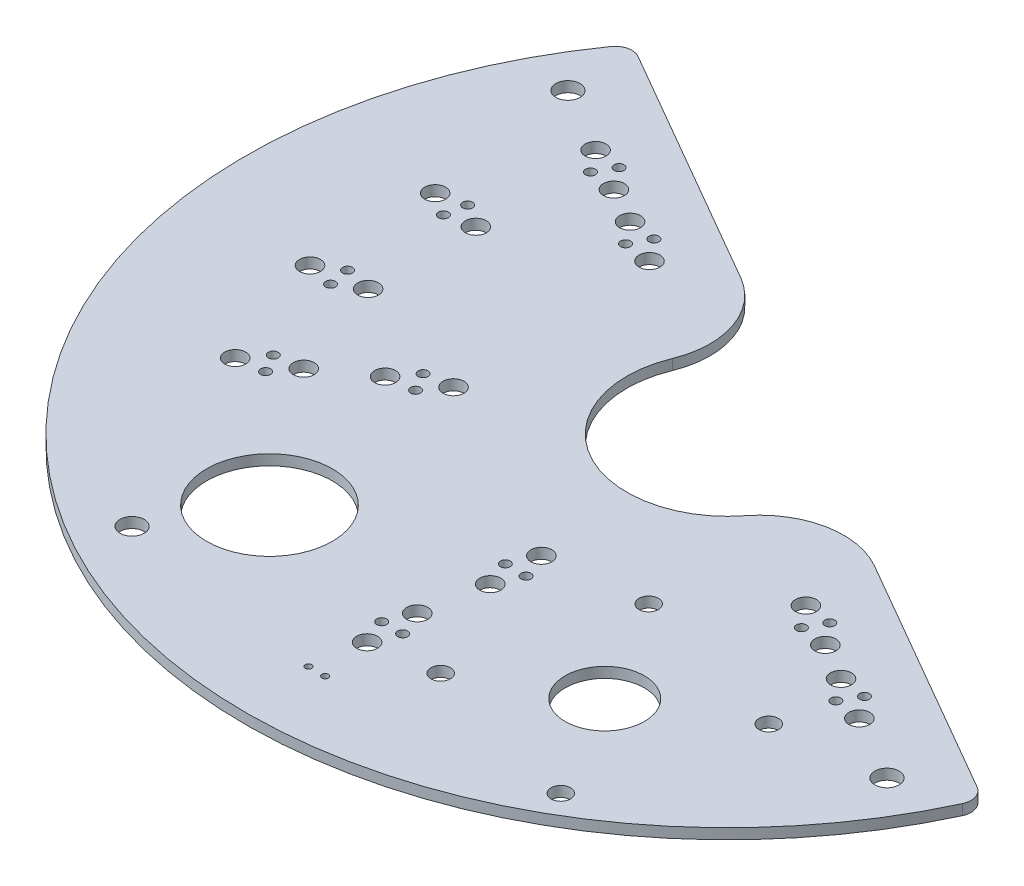
SolidWorks part; units mm, degrees
ref_plane "Front Plane" through (0, 0, 0) normal (0, 0, 1) x (1, 0, 0)
ref_plane "Top Plane" through (0, 0, 0) normal (0, 1, 0) x (1, 0, 0)
ref_plane "Right Plane" through (0, 0, 0) normal (1, 0, 0) x (0, 0, -1)
sketch "Sketch1" plane through (0, 0, 0) normal (0, 1, 0) x (1, 0, 0)
  line L0 (0, 50.8) -> (0, 59.6199) construction
  line L1 (0, 50.8) -> (11.3081, 50.8) construction
  line L2 (0, 0) -> (0, 47) construction
  line L3 (0, 0) -> (-46.286, 8.1615) construction
  line L4 (0, 0) -> (0, 47) construction
  line L5 (0, 0) -> (-46.286, -8.1615) construction
  line L6 (-30.1951, -16.4814) -> (-38.7564, -18.616) construction
  line L7 (1.7716, -33.8648) -> (4.3514, -25.4269) construction
  line L8 (31.2901, -20.38) -> (25.051, -14.141) construction
  line L9 (-31.8057, 17.1605) -> (-38.0448, 23.3996) construction
  circle A0 centre (0, 0) radius 50.8 construction
  circle A1 centre (0, 0) radius 15.24
  circle A2 centre (0, 0) radius 73.025
  circle A3 centre (0, 50.8) radius 6.3 construction
  circle A4 centre (25.4, 43.9941) radius 6.3 construction
  circle A5 centre (43.9941, 25.4) radius 6.3 construction
  circle A6 centre (50.8, 0) radius 6.3 construction
  circle A7 centre (43.9941, -25.4) radius 6.3 construction
  circle A8 centre (25.4, -43.9941) radius 6.3 construction
  circle A9 centre (0, -50.8) radius 6.3 construction
  circle A10 centre (-25.4, -43.9941) radius 6.3 construction
  circle A11 centre (-43.9941, -25.4) radius 6.3 construction
  circle A12 centre (-50.8, 0) radius 6.3 construction
  circle A13 centre (-43.9941, 25.4) radius 6.3 construction
  circle A14 centre (-25.4, 43.9941) radius 6.3 construction
  circle A15 centre (0, 50.8) radius 1.585 construction
  circle A16 centre (-1.585, 50.8) radius 0.75
  circle A17 centre (1.585, 50.8) radius 0.75
  circle A18 centre (0, 50.8) radius 3.8 construction
  circle A19 centre (0, 54.6) radius 1.585
  circle A20 centre (0, 47) radius 1.585
  circle A21 centre (47.285, 27.3) radius 1.585
  circle A22 centre (43.2016, 26.7727) radius 0.75
  circle A23 centre (44.7866, 24.0273) radius 0.75
  circle A24 centre (40.7032, 23.5) radius 1.585
  circle A25 centre (47.285, -27.3) radius 1.585
  circle A26 centre (44.7866, -24.0273) radius 0.75
  circle A27 centre (43.2016, -26.7727) radius 0.75
  circle A28 centre (40.7032, -23.5) radius 1.585
  circle A29 centre (0, -54.6) radius 1.585
  circle A30 centre (1.585, -50.8) radius 0.75
  circle A31 centre (-1.585, -50.8) radius 0.75
  circle A32 centre (0, -47) radius 1.585
  circle A33 centre (-47.285, -27.3) radius 1.585
  circle A34 centre (-43.2016, -26.7727) radius 0.75
  circle A35 centre (-44.7866, -24.0273) radius 0.75
  circle A36 centre (-40.7032, -23.5) radius 1.585
  circle A37 centre (-47.285, 27.3) radius 1.585
  circle A38 centre (-44.7866, 24.0273) radius 0.75
  circle A39 centre (-43.2016, 26.7727) radius 0.75
  circle A40 centre (-40.7032, 23.5) radius 1.585
  circle A41 centre (25.4, 43.9941) radius 20
  circle A42 centre (-25.4, -43.9941) radius 9.525
  circle A43 centre (25.4, -43.9941) radius 6
  circle A44 centre (-46.286, 8.1615) radius 1.585
  circle A45 centre (-50.3035, 7.2604) radius 0.75
  circle A46 centre (-49.753, 10.3822) radius 0.75
  circle A47 centre (-53.7705, 9.4812) radius 1.585
  circle A48 centre (-46.286, -8.1615) radius 1.585
  circle A49 centre (-49.753, -10.3822) radius 0.75
  circle A50 centre (-50.3035, -7.2604) radius 0.75
  circle A51 centre (-53.7705, -9.4812) radius 1.585
  circle A52 centre (-30.191, -16.4817) radius 6.3 construction
  circle A53 centre (-30.191, -16.4817) radius 1.585 construction
  circle A54 centre (-29.3973, -17.8553) radius 0.75
  circle A55 centre (-31.002, -15.1168) radius 0.75
  circle A56 centre (-30.191, -16.4817) radius 3.8 construction
  circle A57 centre (-33.5032, -18.378) radius 1.585
  circle A58 centre (-26.9143, -14.5903) radius 1.585
  circle A59 centre (1.7693, -33.8681) radius 6.3 construction
  circle A60 centre (1.7693, -33.8681) radius 1.585 construction
  circle A61 centre (0.1831, -33.841) radius 0.75
  circle A62 centre (3.3569, -33.8759) radius 0.75
  circle A63 centre (1.7693, -33.8681) radius 3.8 construction
  circle A64 centre (1.8498, -30.0524) radius 1.585
  circle A65 centre (1.7028, -37.651) radius 1.585
  circle A66 centre (31.7545, -18.4007) radius 6.3 construction
  circle A67 centre (31.7545, -18.4007) radius 1.585 construction
  circle A68 centre (30.9859, -19.7885) radius 0.75
  circle A69 centre (32.5067, -17.0026) radius 0.75
  circle A70 centre (31.7545, -18.4007) radius 3.8 construction
  circle A71 centre (28.4231, -16.5382) radius 1.585
  circle A72 centre (35.0633, -20.2353) radius 1.585
  circle A73 centre (-31.9359, 18.6471) radius 6.3 construction
  circle A74 centre (-31.9359, 18.6471) radius 1.585 construction
  circle A75 centre (-32.7045, 17.2593) radius 0.75
  circle A76 centre (-31.1837, 20.0452) radius 0.75
  circle A77 centre (-31.9359, 18.6471) radius 3.8 construction
  circle A78 centre (-35.2672, 20.5095) radius 1.585
  circle A79 centre (-28.627, 16.8125) radius 1.585
  point P50 (0, 0)
  point P84 (0, 0)
  dimension "D1" = 12
  dimension "D2" = 101.6
  dimension "D3" = 3.17
  dimension "D4" = 1.5
  dimension "D5" = 7.6
  dimension "D6" = 6
  dimension "D7" = 3.17
  dimension "D8" = 40
  dimension "D9" = 19.05
  dimension "D10" = 12
  dimension "D11" = 146.05
  dimension "D12" = 30.48
  dimension "D14" = 80
  dimension "D16" = 100
  dimension "D13" = 2
  dimension "D15" = 2
extrude "Boss-Extrude1" add sketch "Sketch1" against normal blind 1.5875
sketch "Sketch2" plane through (0, 0, 0) normal (0, 1, 0) x (1, 0, 0)
  line L0 (0, 0) -> (0, 66.04) construction
  line L1 (0, 0) -> (-57.1923, 33.02) construction
  circle A0 centre (0, 0) radius 66.04 construction
  circle A1 centre (0, 66.04) radius 1.8288 construction
  circle A2 centre (-57.1923, 33.02) radius 1.8288
  circle A3 centre (33.02, 57.1923) radius 1.8288
  circle A4 centre (57.1923, -33.02) radius 1.8288
  circle A5 centre (-33.02, -57.1923) radius 1.8288
  point P17 (0, 0)
  dimension "D1" = 132.08
  dimension "D2" = 3.6576
  dimension "D3" = 2
  dimension "D4" = 60
  dimension "D5" = 4
extrude "Cut-Extrude1" cut sketch "Sketch2" against normal through all
sketch "Sketch3" plane through (0, 0, 0) normal (0, 1, 0) x (1, 0, 0)
  line L0 (-57.1923, 33.02) -> (57.1923, -33.02) construction
  line L1 (-59.5338, 44.6372) -> (68.4238, -29.2392)
  line L2 (-52.7473, 40.719) -> (61.6373, -25.321) construction
  arc A0 (68.4238, -29.2392) -> (-59.5338, 44.6372) centre (0, 0) ccw
  dimension "D1" = 8.89
extrude "Cut-Extrude2" cut sketch "Sketch3" against normal through all
fillet "Fillet1" radius 12.7 2 edges at (15.165, -0.7937, -1.5098) (-6.275, -0.7937, -13.8882)
fillet "Fillet2" radius 2.54 2 edges at (67.2161, -0.7937, 28.542) (-58.3261, -0.7937, -43.9399)
sketch "Sketch4" plane through (0, 0, 0) normal (0, 1, 0) x (1, 0, 0)
  line L0 (0, 0) -> (0, -73.025) construction
  arc A0 (-59.6949, 42.0615) -> (66.2738, -30.6666) centre (0, 0) ccw construction
  circle A1 centre (0, 0) radius 62.23 construction
  circle A2 centre (0, -62.23) radius 0.4953 construction
  circle A3 centre (1.27, -62.23) radius 0.4953
  circle A4 centre (-1.27, -62.23) radius 0.4953
  dimension "D1" = 0.9906
  dimension "D4" = 124.46
  dimension "D2" = 2
  dimension "D3" = 2
extrude "Cut-Extrude3" cut sketch "Sketch4" against normal through all
sketch "Sketch5" plane through (0, -1.5875, 0) normal (0, -1, 0) x (1, 0, 0)
  line L0 (34.4907, 15.2341) -> (45.0238, 21.3018)
  line L1 (-31.0536, -21.3854) -> (-30.5378, -22.2779)
  line L2 (-30.0652, -20.8147) -> (-29.5513, -21.704)
  line L3 (-30.5378, -22.2779) -> (-40.9598, -28.3409)
  line L13 (33.3365, 26.1699) -> (41.5359, 31.0198)
  line L14 (28.0125, 9.134) -> (57.7422, 26.2984)
  line L29 (46.7892, 22.3211) -> (54.7743, 26.9312)
  line L30 (29.0711, 12.1121) -> (33.5009, 14.6639)
  line L31 (6.096, 41.9407) -> (6.096, 51.4811)
  line L32 (32.4795, 23.822) -> (40.9598, 28.3409)
  line L33 (-6.096, 38.6381) -> (-6.096, 51.4811)
  line L34 (4.064, 40.0736) -> (4.064, 49.6426)
  line L35 (-21.9165, -19.6925) -> (-41.5359, -31.0198)
  line L39 (-4.064, 36.8606) -> (-4.064, 49.6426)
  line L40 (-30.4135, 24.5983) -> (-41.5359, 31.0198)
  line L42 (-29.8903, 21.9498) -> (-40.9598, 28.3409)
  line L93 (-25.0455, -19.0828) -> (-29.5513, -21.704)
  arc A0 (1.2946, 63.4357) -> (1.2454, 61.0243) centre (1.27, 62.23) ccw
  arc A1 (-1.1373, 61.0264) -> (-1.1844, 63.4379) centre (-1.27, 62.23) ccw
  arc A2 (-1.1373, 61.0264) -> (-54.0489, -28.3589) centre (0, 0) ccw
  arc A3 (-1.1844, 63.4379) -> (-56.1144, -29.6131) centre (0, 0) ccw
  arc A4 (54.7743, 26.9312) -> (1.2454, 61.0243) centre (0, 0) ccw
  arc A5 (-56.1144, -29.6131) -> (-54.0489, -28.3589) centre (-55.1689, -28.8424) ccw
  arc A6 (6.096, 51.4811) -> (2.3857, 51.7858) centre (0, 0) ccw
  arc A7 (32.4795, 23.822) -> (4.064, 40.0736) centre (0, 0) ccw
  arc A8 (2.3857, 51.7858) -> (2.3071, 49.7553) centre (1.585, 50.8) ccw
  arc A9 (-2.3071, 49.7553) -> (-2.3857, 51.7858) centre (-1.585, 50.8) ccw
  arc A10 (-48.5987, -10.912) -> (-50.5848, -11.342) centre (-49.753, -10.3822) ccw
  arc A11 (-51.4133, -6.6431) -> (-49.4, -6.3679) centre (-50.3035, -7.2604) ccw
  arc A12 (46.0407, 23.8268) -> (44.2429, 22.8796) centre (44.7866, 24.0273) ccw
  arc A13 (41.9358, 26.8756) -> (43.655, 27.959) centre (43.2016, 26.7727) ccw
  arc A14 (-49.4, 6.3679) -> (-51.4133, 6.6431) centre (-50.3035, 7.2604) ccw
  arc A15 (-50.5848, 11.342) -> (-48.5987, 10.912) centre (-49.753, 10.3822) ccw
  arc A16 (57.7422, 26.2984) -> (1.2946, 63.4357) centre (0, 0) ccw
  arc A17 (-2.3857, 51.7858) -> (-6.096, 51.4811) centre (0, 0) ccw
  arc A18 (-2.3071, 49.7553) -> (-4.064, 49.6426) centre (0, 0) ccw
  arc A19 (45.0238, 21.3018) -> (44.2429, 22.8796) centre (0, 0) ccw
  arc A20 (29.0711, 12.1121) -> (-25.0455, -19.0828) centre (2.3366, -4.0471) ccw
  arc A21 (28.0125, 9.134) -> (-21.9165, -19.6925) centre (2.3859, -4.1326) ccw
  arc A22 (46.7892, 22.3211) -> (46.0407, 23.8268) centre (0, 0) ccw
  arc A23 (43.655, 27.959) -> (41.5359, 31.0198) centre (0, 0) ccw
  arc A24 (-46.0407, -23.8268) -> (-44.2429, -22.8796) centre (-44.7866, -24.0273) ccw
  arc A25 (-41.9358, -26.8756) -> (-43.655, -27.959) centre (-43.2016, -26.7727) ccw
  arc A26 (41.9358, 26.8756) -> (40.9598, 28.3409) centre (0, 0) ccw
  circle A27 centre (1.27, 62.23) radius 0.4953
  arc A28 (-43.655, 27.959) -> (-41.9358, 26.8756) centre (-43.2016, 26.7727) ccw
  arc A29 (-44.2429, 22.8796) -> (-46.0407, 23.8268) centre (-44.7866, 24.0273) ccw
  circle A30 centre (-1.27, 62.23) radius 0.4953
  arc A31 (-43.655, -27.959) -> (-41.5359, -31.0198) centre (0, 0) ccw
  circle A32 centre (-26.7727, 43.2016) radius 1.27 [skipped]
  circle A33 centre (-24.0273, 44.7866) radius 1.27 [skipped]
  circle A34 centre (24.0273, 44.7866) radius 1.27 [skipped]
  circle A35 centre (26.7727, 43.2016) radius 1.27 [skipped]
  circle A36 centre (50.8, 1.585) radius 1.27 [skipped]
  circle A37 centre (50.8, -1.585) radius 1.27 [skipped]
  circle A38 centre (44.7866, -24.0273) radius 1.27 [skipped]
  circle A39 centre (43.2016, -26.7727) radius 1.27 [skipped]
  circle A40 centre (26.7727, -43.2016) radius 1.27 [skipped]
  circle A41 centre (24.0273, -44.7866) radius 1.27 [skipped]
  circle A42 centre (1.585, -50.8) radius 1.27 [skipped]
  circle A43 centre (-1.585, -50.8) radius 1.27 [skipped]
  circle A44 centre (-24.0273, -44.7866) radius 1.27 [skipped]
  circle A45 centre (-26.7727, -43.2016) radius 1.27 [skipped]
  circle A46 centre (-50.8, 1.585) radius 1.27 [skipped]
  circle A47 centre (-50.8, -1.585) radius 1.27 [skipped]
  arc A48 (-41.9358, -26.8756) -> (-40.9598, -28.3409) centre (0, 0) ccw
  arc A49 (-40.9598, 28.3409) -> (-41.9358, 26.8756) centre (0, 0) ccw
  arc A50 (33.3365, 26.1699) -> (6.096, 41.9407) centre (0, 0) ccw
  circle A51 centre (1.585, 50.8) radius 0.75
  arc A52 (-46.0407, 23.8268) -> (-47.6319, 20.4612) centre (0, 0) ccw
  arc A53 (4.064, 49.6426) -> (2.3071, 49.7553) centre (0, 0) ccw
  arc A54 (-41.5359, 31.0198) -> (-43.655, 27.959) centre (0, 0) ccw
  arc A55 (-6.096, 38.6381) -> (-30.4135, 24.5983) centre (0, 0) ccw
  arc A56 (-4.064, 36.8606) -> (-29.8903, 21.9498) centre (0, 0) ccw
  arc A57 (-44.2429, 22.8796) -> (-48.5987, 10.912) centre (0, 0) ccw
  circle A58 centre (-1.585, 50.8) radius 0.75
  circle A59 centre (43.2016, 26.7727) radius 0.75
  arc A60 (-47.6319, 20.4612) -> (-50.5848, 11.342) centre (0, 0) ccw
  arc A61 (-51.4133, 6.6431) -> (-51.4133, -6.6431) centre (0, 0) ccw
  arc A62 (-49.4, 6.3679) -> (-49.4, -6.3679) centre (0, 0) ccw
  circle A63 centre (44.7866, 24.0273) radius 0.75
  arc A64 (-50.5848, -11.342) -> (-46.0407, -23.8268) centre (0, 0) ccw
  arc A65 (-48.5987, -10.912) -> (-44.2429, -22.8796) centre (0, 0) ccw
  circle A66 centre (-43.2016, 26.7727) radius 0.75
  circle A67 centre (-44.7866, 24.0273) radius 0.75
  circle A68 centre (-49.753, 10.3822) radius 0.75
  circle A69 centre (-50.3035, 7.2604) radius 0.75
  circle A70 centre (-50.3035, -7.2604) radius 0.75
  circle A71 centre (-49.753, -10.3822) radius 0.75
  circle A72 centre (-44.7866, -24.0273) radius 0.75
  circle A73 centre (-43.2016, -26.7727) radius 0.75
  arc A74 (29.7503, 20.2948) -> (30.8424, 21.1896) centre (30.9918, 19.8934) ccw
  arc A75 (4.5236, 34.6192) -> (30.8424, 21.1896) centre (5.7054, 4.4312) cw
  arc A76 (4.4841, 33.194) -> (29.7503, 20.2948) centre (4.8534, 2.7227) cw
  arc A77 (33.7473, 16.7292) -> (32.8413, 15.8053) centre (32.514, 17.0324) ccw
  arc A78 (33.5009, 14.6639) -> (32.8413, 15.8053) centre (-9.9501, -9.686) ccw
  arc A79 (34.4907, 15.2341) -> (33.7473, 16.7292) centre (-12.2934, -7.0976) ccw
  arc A80 (-0.8928, 32.9745) -> (-0.4432, 34.9562) centre (0.075, 33.7967) ccw
  arc A81 (-29.697, 19.0828) -> (-0.4432, 34.9562) centre (2.1808, -4.7732) cw
  arc A82 (4.5236, 34.6192) -> (4.4841, 33.194) centre (3.4532, 33.9357) ccw
  circle A83 centre (-31.1738, -20.0389) radius 0.75
  arc A84 (-29.697, 19.0828) -> (-28.1584, 17.7555) centre (-29.4254, 17.8422) ccw
  arc A85 (-28.1584, 17.7555) -> (-0.8928, 32.9745) centre (0.881, -2.2367) cw
  arc A86 (-31.3368, 13.0383) -> (-32.985, 14.2011) centre (-31.3367, 14.7878) ccw
  arc A87 (-32.985, 14.2011) -> (-34.3304, 11.6344) centre (112.8254, -63.8668) ccw
  arc A88 (-33.9153, -16.8172) -> (-31.9293, -16.3872) centre (-32.7611, -17.3469) ccw
  arc A89 (-31.9293, -16.3872) -> (-32.6415, -14.9048) centre (-79.0072, -38.0929) ccw
  arc A90 (-30.0652, -20.8147) -> (-31.0536, -21.3854) centre (-31.1268, -20.1175) ccw
  circle A91 centre (-32.7183, -17.2601) radius 0.75
  arc A92 (-34.3304, 11.6344) -> (-33.9153, -16.8172) centre (-7.3644, -2.2011) ccw
  arc A93 (-31.3368, 13.0383) -> (-32.6415, -14.9048) centre (-7.0347, -2.0984) ccw
  circle A94 centre (-31.007, 15.1229) radius 0.75
  circle A95 centre (-29.3984, 17.8491) radius 0.75
  circle A96 centre (0.1843, 33.8387) radius 0.75
  circle A97 centre (3.3549, 33.875) radius 0.75
  circle A98 centre (30.9845, 19.7892) radius 0.75
  circle A99 centre (32.5074, 16.9933) radius 0.75
  dimension "D13" = 12
  dimension "D15" = 3
extrude "Boss-Extrude2" add sketch "Sketch5" along normal blind 0.1016
sketch "Sketch6" plane through (0, -1.5875, 0) normal (0, -1, 0) x (1, 0, 0)
  line L0 (0, 0) -> (25.4, 43.9941) construction
  line L1 (25.4, 43.9941) -> (36.5125, 63.2415) construction
  circle A0 centre (25.4, 43.9941) radius 18.1937 construction
  arc A1 (66.2738, 30.6666) -> (-59.6949, -42.0615) centre (0, 0) ccw construction
  circle A2 centre (34.4969, 59.7503) radius 1.4732
  circle A3 centre (9.6438, 53.0909) radius 1.4732
  circle A4 centre (16.3031, 28.2379) radius 1.4732
  circle A5 centre (41.1562, 34.8972) radius 1.4732
  point P20 (25.4, 43.9941)
  dimension "D1" = 2.9464
extrude "Cut-Extrude4" cut sketch "Sketch6" against normal through all
